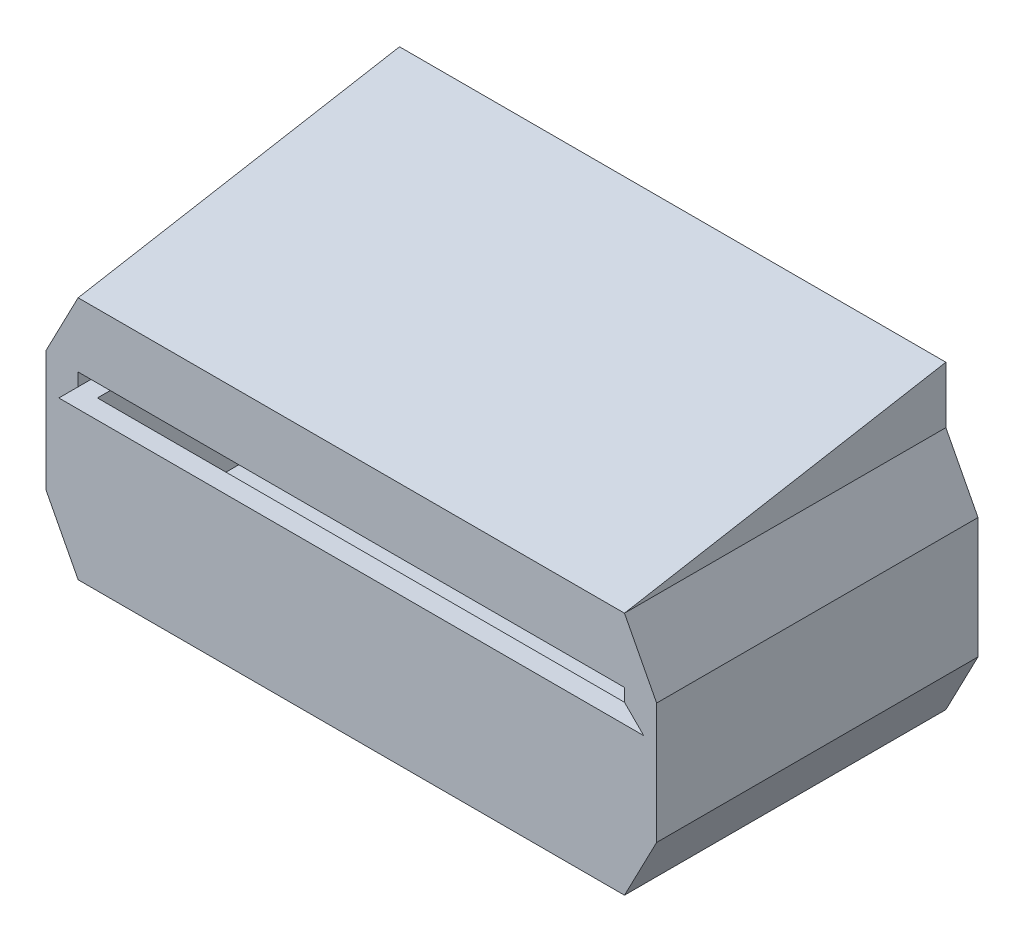
SolidWorks part; units mm, degrees
ref_plane "Front Plane" through (0, 0, 0) normal (0, 0, 1) x (1, 0, 0)
ref_plane "Top Plane" through (0, 0, 0) normal (0, 1, 0) x (1, 0, 0)
ref_plane "Right Plane" through (0, 0, 0) normal (1, 0, 0) x (0, 0, -1)
sketch "Sketch1" plane through (0, 0, 0) normal (0, 1, 0) x (1, 0, 0)
  line L1 (0, 0) -> (85, 0)
  line L2 (0, 0) -> (0, 90)
  line L3 (0, 90) -> (85, 90)
  line L4 (85, 0) -> (85, 90)
  dimension "D1" = 85
  dimension "D2" = 90
extrude "Boss-Extrude1 (Base)" add sketch "Sketch1" along normal blind 3
sketch "Sketch4" plane through (0, 0, 0) normal (0, 0, 1) x (1, 0, 0)
  line L0 (-3, 23) -> (0, 26)
  line L1 (0, 26) -> (0, 23)
  line L2 (0, 23) -> (-3, 23)
  line L3 (0, 3) -> (85, 3) construction
  line L6 (0, 3) -> (0, 0) construction
  line L7 (42.5, 28.9013) -> (42.5, -8.4397) construction
  line L8 (85, 3) -> (85, 0) construction
  line L9 (85, 23) -> (88, 23)
  line L10 (85, 26) -> (85, 23)
  line L11 (88, 23) -> (85, 26)
  dimension "D1" = 20
  dimension "D2" = 3
  dimension "D3" = 3
  dimension "D4" = 42.5
sketch "Sketch5" plane through (0, 0, 0) normal (0, 0, 1) x (1, 0, 0)
  line L6 (42.5, 3) -> (42.5, 26.9028) construction
  line L11 (-5, 28.3909) -> (0, 38)
  line L12 (0, 38) -> (0, 0)
  line L13 (0, 0) -> (-5, 9.6091)
  line L14 (-5, 9.6091) -> (-5, 28.3909)
  line L15 (90, 9.6091) -> (90, 28.3909)
  line L16 (0, 3) -> (85, 3) construction
  line L21 (85, 0) -> (90, 9.6091)
  line L22 (85, 38) -> (85, 0)
  line L23 (90, 28.3909) -> (85, 38)
  dimension "D1" = 5
  dimension "D2" = 35
extrude "Boss-Extrude4 (Side Walls)" add sketch "Sketch5" against normal through all
extrude "Cut-Extrude2 (Guide Holes)" cut sketch "Sketch4" against normal through all
sketch "Sketch15" plane through (0, 0, 0) normal (0, 0, 1) x (1, 0, 0)
  line L0 (85, 23) -> (85, 3) construction
  line L1 (0, 23) -> (85, 23)
  line L2 (0, 23) -> (0, 3)
  line L3 (0, 3) -> (85, 3)
  line L4 (85, 23) -> (85, 3)
extrude "Boss-Extrude9 (Rear Wall)" add sketch "Sketch15" against normal blind 3
sketch "Sketch17" plane through (0, 23, 0) normal (0, 1, 0) x (1, 0, 0)
  line L1 (85, 3) -> (0, 3)
  line L2 (85, 3) -> (85, 0)
  line L3 (85, 0) -> (0, 0)
  line L4 (0, 3) -> (0, 0)
extrude "Boss-Extrude1 (Rear Wall)" add sketch "Sketch17" along normal blind 12 from offset 3
sketch "Sketch30" plane through (0, 0, 0) normal (0, 0, 1) x (1, 0, 0)
  line L1 (0, 26) -> (85, 26)
  line L2 (0, 26) -> (0, 28)
  line L3 (0, 28) -> (85, 28)
  line L4 (85, 26) -> (85, 28)
  dimension "D1" = 2
extrude "Cut-Extrude1 (Rear Wall)" cut sketch "Sketch30" against normal blind 10
sketch "Sketch20" plane through (0, 3, 0) normal (0, 1, 0) x (1, 0, 0)
  line L0 (85, 90) -> (0, 90) construction
  line L1 (0, 3) -> (3, 3)
  line L2 (0, 3) -> (0, 90)
  line L3 (0, 90) -> (3, 90)
  line L4 (3, 3) -> (3, 90)
  line L5 (42.5, 90) -> (42.5, 70.8429) construction
  line L6 (85, 3) -> (0, 3) construction
  line L7 (0, 3) -> (0, 0) construction
  line L8 (82, 3) -> (82, 90)
  line L9 (85, 90) -> (82, 90)
  line L10 (85, 3) -> (85, 90)
  line L11 (85, 3) -> (82, 3)
  dimension "D1" = 3
extrude "Boss-Extrude2 (Side Wall)" add sketch "Sketch20" along normal blind 10 from offset 25
chamfer "Chamfer1 (Side Wall)" distance 3 angle 45 2 edges at (82, 28, -46.5) (3, 28, -46.5)
sketch "Sketch26" plane through (0, 38, 0) normal (0, 1, 0) x (1, 0, 0)
  line L3 (0, 0) -> (0, 90)
  line L4 (0, 90) -> (0, 0) construction
  line L5 (0, 90) -> (3, 90)
  line L6 (3, 90) -> (0, 90) construction
  line L7 (3, 90) -> (3, 3)
  line L12 (3, 3) -> (82, 3)
  line L13 (82, 3) -> (82, 90)
  line L14 (82, 90) -> (85, 90)
  line L15 (85, 90) -> (85, 0)
  line L16 (85, 0) -> (0, 0)
extrude "Boss-Extrude5 (Side Wall)" add sketch "Sketch26" along normal blind 30
chamfer "Chamfer2 (Roof)" distance 30 angle 80 1 edges at (42.5, 68, 0) first distance on face at (42.5, 25.6667, 0)
sketch "Sketch28" plane through (0, 36.8542, 6.4984) normal (0, 0.9848, 0.1736) x (1, 0, 0)
  line L1 (85, 97.987) -> (0, 97.987)
  line L2 (85, 97.987) -> (85, 6.5986)
  line L3 (85, 6.5986) -> (0, 6.5986)
  line L4 (0, 97.987) -> (0, 6.5986)
extrude "Boss-Extrude7 (Roof)" add sketch "Sketch28" against normal blind 3
sketch "Sketch29" plane through (90, 0, 0) normal (1, 0, 0) x (0, 0, -1)
  line L1 (90, 0) -> (98.083, 0)
  line L2 (90, 0) -> (90, 55.5979)
  line L3 (90, 55.5979) -> (98.083, 55.5979)
  line L4 (98.083, 0) -> (98.083, 55.5979)
extrude "Cut-Extrude1 (Clean up)" cut sketch "Sketch29" against normal through all
sketch "Sketch31" plane through (0, 0, 0) normal (0, -1, 0) x (1, 0, 0)
  line L0 (90, -90) -> (90, 0) construction
  line L1 (-5, -90) -> (90, -90)
  line L2 (-5, -90) -> (-5, -50)
  line L3 (-5, -50) -> (90, -50)
  line L4 (90, -90) -> (90, -50)
  line L5 (0, 0) -> (85, 0) construction
  dimension "D1" = 50
extrude "Cut-Extrude2 (Clean Up)" cut sketch "Sketch31" against normal through all
